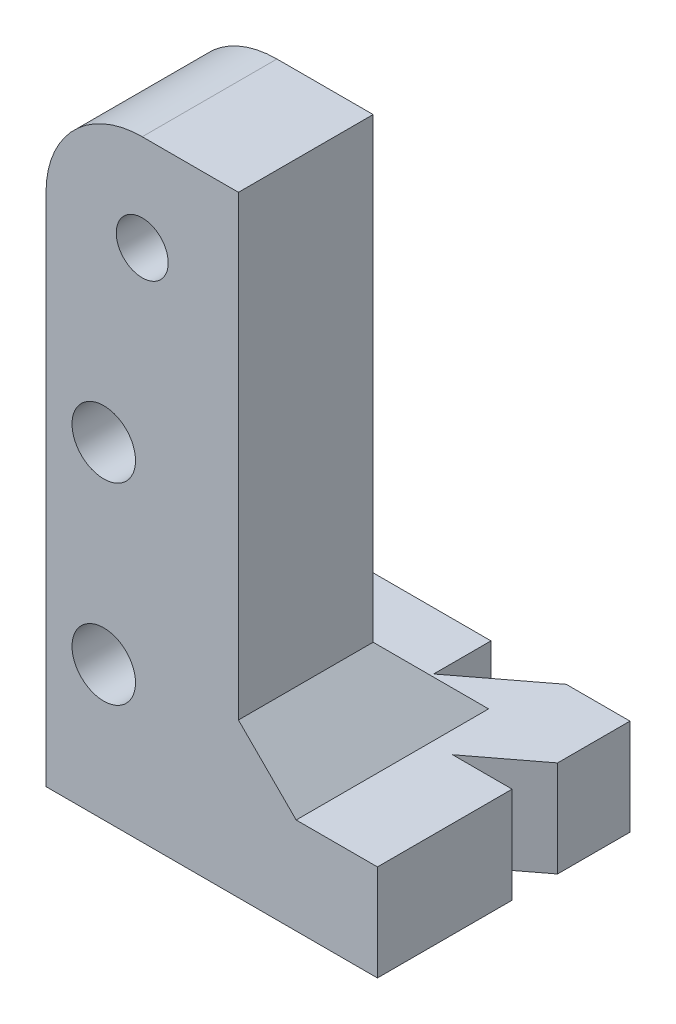
SolidWorks part; units mm, degrees
ref_plane "前视基准面" through (0, 0, 0) normal (0, 0, 1) x (1, 0, 0)
ref_plane "上视基准面" through (0, 0, 0) normal (0, 1, 0) x (1, 0, 0)
ref_plane "右视基准面" through (0, 0, 0) normal (1, 0, 0) x (0, 0, -1)
sketch "草图1" plane through (0, 0, 0) normal (0, 1, 0) x (1, 0, 0)
  line L1 (-31, -23) -> (31, -23)
  line L2 (-31, -23) -> (-31, 23)
  line L3 (-31, 23) -> (31, 23)
  line L4 (31, -23) -> (31, 23)
  line L5 (-31, -23) -> (31, 23) construction
  line L6 (-31, 23) -> (31, -23) construction
  point P0 (0, 0)
  dimension "D1" = 62
  dimension "D2" = 46
extrude "凸台-拉伸1" add sketch "草图1" along normal blind 5
sketch "草图2" plane through (0, 0, 23) normal (0, 0, 1) x (1, 0, 0)
  line L1 (-31, 5) -> (-21, 5)
  line L2 (-31, 5) -> (-31, 22)
  line L3 (-31, 22) -> (-21, 22)
  line L4 (-21, 5) -> (-21, 22)
  line L5 (31, 5) -> (21, 5)
  line L6 (31, 5) -> (31, 22)
  line L7 (31, 22) -> (21, 22)
  line L8 (21, 5) -> (21, 22)
  dimension "D1" = 17
  dimension "D2" = 10
extrude "凸台-拉伸2" add sketch "草图2" against normal blind 7
sketch "草图3" plane through (0, 0, 23) normal (0, 0, 1) x (1, 0, 0)
  line L0 (-21, 22) -> (21, 22) construction
  line L1 (0, 22) -> (0, 12) construction
  line L2 (-28, 7) -> (28, 7) construction
  line L3 (-28, 7) -> (-28, 17) construction
  line L4 (-28, 17) -> (28, 17) construction
  line L5 (28, 7) -> (28, 17) construction
  line L6 (-28, 7) -> (28, 17) construction
  line L7 (-28, 17) -> (28, 7) construction
  circle A0 centre (-28, 17) radius 1.65
  circle A1 centre (-28, 7) radius 1.65
  circle A2 centre (28, 7) radius 1.65
  circle A3 centre (28, 17) radius 1.65
  point P4 (0, 12)
  dimension "D3" = 3.3
  dimension "D1" = 10
  dimension "D2" = 56
  dimension "D4" = 10
extrude "切除-拉伸1" cut sketch "草图3" against normal blind 12
sketch "草图7" plane through (0, 22, 0) normal (0, 1, 0) x (1, 0, 0)
  line L1 (-31, -23) -> (-21, -23)
  line L2 (-31, -23) -> (-31, -16)
  line L3 (-31, -16) -> (-21, -16)
  line L4 (-21, -23) -> (-21, -16)
  line L5 (21, -23) -> (31, -23)
  line L6 (21, -23) -> (21, -16)
  line L7 (21, -16) -> (31, -16)
  line L8 (31, -23) -> (31, -16)
extrude "凸台-拉伸4" add sketch "草图7" along normal blind 9.75
sketch "草图8" plane through (0, 0, 23) normal (0, 0, 1) x (1, 0, 0)
  line L0 (-26, 31.75) -> (-26, 26.75) construction
  line L1 (-31, 31.75) -> (-21, 31.75) construction
  line L2 (26, 31.75) -> (26, 26.75) construction
  line L3 (21, 31.75) -> (31, 31.75) construction
  line L4 (-26, 26.75) -> (26, 26.75) construction
  circle A0 centre (-26, 26.75) radius 1.35
  circle A1 centre (26, 26.75) radius 1.35
  dimension "D2" = 2.7
  dimension "D1" = 5
extrude "切除-拉伸4" cut sketch "草图8" against normal up to next
ref_plane "基准面1" through (0, 0, 20.5) normal (0, 0, 1) x (1, 0, 0)
sketch "草图4" plane through (0, 0, 20.5) normal (0, 0, 1) x (1, 0, 0)
  line L0 (-29.6166, 19.8) -> (-31.2332, 19.8)
  line L1 (-24.7668, 17) -> (-26.3834, 19.8)
  line L2 (-26.3834, 19.8) -> (-29.6166, 19.8)
  line L3 (-29.6166, 19.8) -> (-31.2332, 17) construction
  line L4 (-31.2332, 17) -> (-29.6166, 14.2) construction
  line L5 (-29.6166, 14.2) -> (-26.3834, 14.2)
  line L6 (-26.3834, 14.2) -> (-24.7668, 17)
  line L7 (-24.7668, 7) -> (-26.3834, 9.8)
  line L8 (-26.3834, 9.8) -> (-29.6166, 9.8)
  line L9 (-29.6166, 9.8) -> (-31.2332, 7) construction
  line L10 (-31.2332, 7) -> (-29.6166, 4.2) construction
  line L11 (-29.6166, 4.2) -> (-26.3834, 4.2)
  line L12 (-26.3834, 4.2) -> (-24.7668, 7)
  line L13 (24.7668, 17) -> (26.3834, 14.2)
  line L14 (26.3834, 14.2) -> (29.6166, 14.2)
  line L15 (29.6166, 14.2) -> (31.2332, 17) construction
  line L16 (31.2332, 17) -> (29.6166, 19.8) construction
  line L17 (29.6166, 19.8) -> (26.3834, 19.8)
  line L18 (26.3834, 19.8) -> (24.7668, 17)
  line L19 (24.7668, 7) -> (26.3834, 4.2)
  line L20 (26.3834, 4.2) -> (29.6166, 4.2)
  line L21 (29.6166, 4.2) -> (31.2332, 7) construction
  line L22 (31.2332, 7) -> (29.6166, 9.8) construction
  line L23 (29.6166, 9.8) -> (26.3834, 9.8)
  line L24 (26.3834, 9.8) -> (24.7668, 7)
  line L25 (-31.2332, 19.8) -> (-31.2332, 17)
  line L26 (-29.6166, 14.2) -> (-31.2332, 14.2)
  line L27 (-31.2332, 14.2) -> (-31.2332, 17)
  line L28 (-29.6166, 9.8) -> (-31.2332, 9.8)
  line L29 (-31.2332, 9.8) -> (-31.2332, 7)
  line L30 (-29.6166, 4.2) -> (-31.2332, 4.2)
  line L31 (-31.2332, 4.2) -> (-31.2332, 7)
  line L32 (29.6166, 19.8) -> (31.2332, 19.8)
  line L33 (31.2332, 19.8) -> (31.2332, 17)
  line L34 (29.6166, 14.2) -> (31.2332, 14.2)
  line L35 (31.2332, 14.2) -> (31.2332, 17)
  line L36 (29.6166, 9.8) -> (31.2332, 9.8)
  line L37 (31.2332, 9.8) -> (31.2332, 7)
  line L38 (31.2332, 7) -> (31.2332, 4.2)
  line L39 (31.2332, 4.2) -> (29.6166, 4.2)
  circle A0 centre (-28, 17) radius 2.8 construction
  circle A1 centre (-28, 7) radius 2.8 construction
  circle A2 centre (28, 17) radius 2.8 construction
  circle A3 centre (28, 7) radius 2.8 construction
  dimension "D1" = 5.6
extrude "切除-拉伸2" cut sketch "草图4" against normal blind 2.7
mirror "镜向1" about plane through (0, 0, 0) normal (0, 0, 1) of "切除-拉伸4", "凸台-拉伸2", "切除-拉伸1", "切除-拉伸2", "凸台-拉伸4"
sketch "草图5" plane through (0, 31.75, 0) normal (0, 1, 0) x (1, 0, 0)
  line L1 (-21, -16) -> (21, -16)
  line L2 (-21, -16) -> (-21, 16)
  line L3 (-21, 16) -> (21, 16)
  line L4 (21, -16) -> (21, 16)
extrude "切除-拉伸3" cut sketch "草图5" against normal up to next
sketch "草图6" plane through (0, 0, 0) normal (0, 1, 0) x (1, 0, 0)
  line L0 (19.4849, -17.9886) -> (-22.5151, 14.0114)
  line L1 (19.4849, -17.9886) -> (22.5151, -14.0114)
  line L2 (-22.5151, 14.0114) -> (-19.4849, 17.9886)
  line L3 (22.5151, -14.0114) -> (-19.4849, 17.9886)
  line L4 (-21, 16) -> (21, -16) construction
  line L5 (-1.5151, -1.9886) -> (1.5151, 1.9886) construction
  line L6 (-22.5151, -14.0114) -> (19.4849, 17.9886)
  line L7 (-22.5151, -14.0114) -> (-19.4849, -17.9886)
  line L8 (19.4849, 17.9886) -> (22.5151, 14.0114)
  line L9 (-19.4849, -17.9886) -> (22.5151, 14.0114)
  line L10 (21, 16) -> (-21, -16) construction
  line L11 (-1.5151, 1.9886) -> (1.5151, -1.9886) construction
  point P1 (0, 0)
  point P2 (0, 0)
  dimension "D1" = 5
extrude "凸台-拉伸3" add sketch "草图6" along normal up to surface (5 mm away) contours L0 L6 L3 L2 | L3 L9 L8 L6 | L0 L9 L3 L6 | L7 L9 L0 L6 | L9 L0 L1 L3 region at (11.514, 0, 8.8029) region at (-11.514, 0, 8.8029) region at (0, 0, 0) region at (-11.514, 0, -8.8029) region at (11.514, 0, -8.8029) up to face at (0, 5, -19.5)
chamfer "倒角4" distance 3 angle 45 8 edges at (-21, 5, 19.5) (21, 5, 19.5) (26, 5, -16) (21, 5, -19.5) (-26, 5, -16) (-21, 5, -19.5) (-26, 5, 16) (26, 5, 16)
fillet "圆角1" radius 5 4 edges at (31, 31.75, -19.5) (31, 31.75, 19.5) (-31, 31.75, 19.5) (-31, 31.75, -19.5)
sketch "草图9" plane through (0, 0, 0) normal (0, 1, 0) x (1, 0, 0)
  line L1 (-33.5214, -28.3036) -> (-13.7771, -28.3036)
  line L2 (-33.5214, -28.3036) -> (-33.5214, -9.8755)
  line L3 (-33.5214, -9.8755) -> (-13.7771, -9.8755)
  line L4 (-13.7771, -28.3036) -> (-13.7771, -9.8755)
extrude "切除-拉伸5" cut sketch "草图9" along normal up to surface (31.75 mm away) flip side to cut up to face at (-23.5, 31.75, 19.5)
